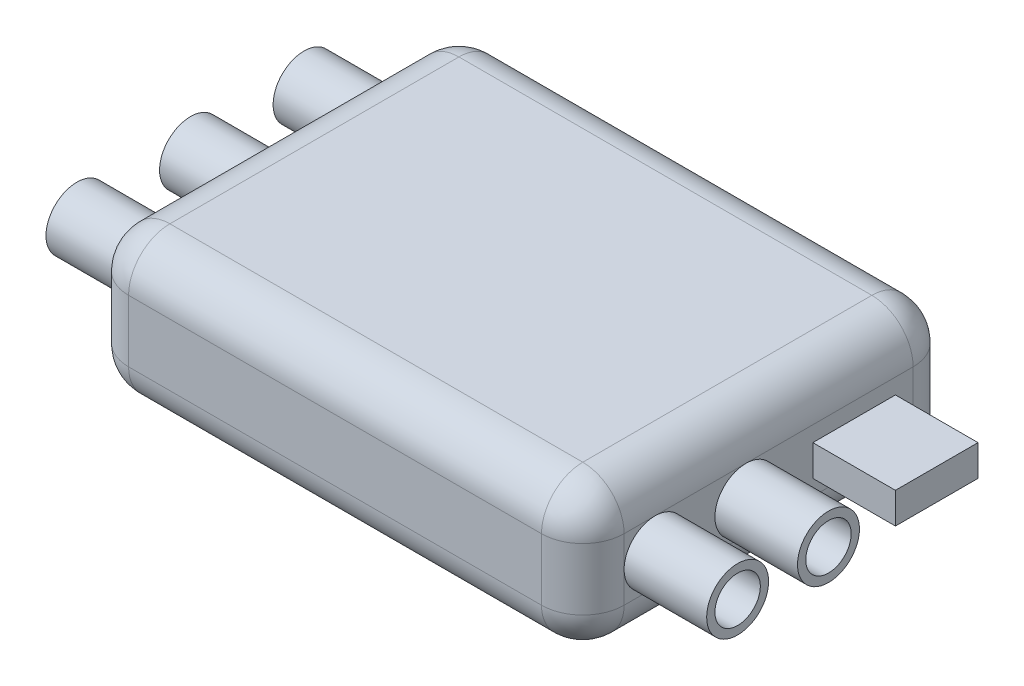
SolidWorks part; units mm, degrees
ref_plane "Front Plane" through (0, 0, 0) normal (0, 0, 1) x (1, 0, 0)
ref_plane "Top Plane" through (0, 0, 0) normal (0, 1, 0) x (1, 0, 0)
ref_plane "Right Plane" through (0, 0, 0) normal (1, 0, 0) x (0, 0, -1)
sketch "Sketch1" plane through (0, 0, 0) normal (0, 1, 0) x (1, 0, 0)
  line L1 (10, -9) -> (-10, -9)
  line L2 (12, -7) -> (12, 7)
  line L3 (10, 9) -> (-10, 9)
  line L4 (-12, -7) -> (-12, 7)
  line L5 (12, -9) -> (-12, 9) construction
  line L6 (12, 9) -> (-12, -9) construction
  arc A0 (12, 7) -> (10, 9) centre (10, 7) ccw
  arc A1 (10, -9) -> (12, -7) centre (10, -7) ccw
  arc A2 (-10, -9) -> (-12, -7) centre (-10, -7) cw
  arc A3 (-10, 9) -> (-12, 7) centre (-10, 7) ccw
  point P0 (0, 0)
  dimension "D3" = 2
  dimension "D1" = 24
  dimension "D2" = 18
extrude "Boss-Extrude1" add sketch "Sketch1" against normal blind 7
sketch "Sketch3" plane through (0, 0, 0) normal (0, 1, 0) x (1, 0, 0)
  line L0 (-12, 7) -> (12, 7)
  line L1 (-12, -7) -> (12, -7)
  line L2 (-10, 9) -> (-10, -9)
  line L3 (10, 9) -> (10, -9)
sketch "Sketch5" plane through (-12, 0, 0) normal (-1, 0, 0) x (0, 0, 1)
  line L0 (-9, 0) -> (9, 0) construction
  line L1 (-7, 0) -> (7, 0)
  line L2 (-9, -7) -> (-9, 0) construction
  line L3 (-9, -5) -> (-9, -2)
  line L4 (-7, -7) -> (7, -7)
  line L5 (9, -5) -> (9, -2)
  line L6 (-9, -2) -> (-9, 0)
  line L7 (-9, 0) -> (-7, 0)
  line L8 (-9, -5) -> (-9, -7)
  line L9 (-9, -7) -> (-7, -7)
  line L10 (7, -7) -> (9, -7)
  line L11 (9, -7) -> (9, -5)
  line L12 (7, 0) -> (9, 0)
  line L13 (9, 0) -> (9, -2)
  arc A0 (7, 0) -> (9, -2) centre (7, -2) cw
  arc A1 (7, -7) -> (9, -5) centre (7, -5) ccw
  arc A2 (-9, -5) -> (-7, -7) centre (-7, -5) ccw
  arc A3 (-7, 0) -> (-9, -2) centre (-7, -2) ccw
  point P10 (9, -7)
  dimension "D1" = 2
sketch "Sketch6" plane through (0, -7, 0) normal (0, -1, 0) x (1, 0, 0)
  line L0 (-12, 7) -> (12, 7) construction
  line L1 (-12, 7) -> (12, 7) construction
  line L2 (-10, -9) -> (-10, 9) construction
  line L3 (-10, -9) -> (-10, 9) construction
  line L4 (10, -9) -> (10, 9) construction
  line L5 (10, -9) -> (10, 9) construction
  line L6 (-12, -7) -> (12, -7) construction
  line L7 (-12, -7) -> (12, -7) construction
extrude "Cut-Extrude3" cut sketch "Sketch5" against normal through all contours A3 L7 L6 | A2 L8 L9 | A1 L10 L11 | L12 A0 L13 region at (-12, -0.4467, -8.5533) region at (-12, -0.4467, 8.5533) region at (-12, -6.5533, -8.5533) region at (-12, -6.5533, 8.5533)
sketch "Sketch7" plane through (-12, 0, 0) normal (-1, 0, 0) x (0, 0, 1)
  line L0 (-9, -2) -> (9, -2)
  line L1 (-9, -5) -> (9, -5)
  line L2 (-9, -3.5) -> (9, -3.5) construction
  line L3 (-9, -5) -> (-9, -2) construction
  line L4 (9, -5) -> (9, -2) construction
  line L5 (-7, -2) -> (-7, -5) construction
  line L6 (-7, -7) -> (-7, 0) construction
  line L7 (-7, -5) -> (7, -5) construction
  line L8 (0, 0) -> (0, -7) construction
  line L9 (-9, -7) -> (9, -7) construction
  line L10 (7, -2) -> (7, -5) construction
  arc A0 (7, -7) -> (9, -5) centre (7, -5) ccw construction
  circle A1 centre (-5.5, -3.5) radius 1.5
  circle A2 centre (0, -3.5) radius 1.5
  circle A3 centre (5.5, -3.5) radius 1.5
  circle A4 centre (-5.5, -3.5) radius 1.1
  circle A5 centre (0, -3.5) radius 1.1
  circle A6 centre (5.5, -3.5) radius 1.1
  point P32 (0, -3.5)
  dimension "D3" = 2.2
  dimension "D1" = 1.5
  dimension "D2" = 1.5
extrude "Boss-Extrude3" add sketch "Sketch7" along normal blind 4 contours A1 A4 | A2 A5 | A3 A6 region at (-12, -2.4693, -4.4693) region at (-12, -2.4693, 1.0307) region at (-12, -2.4693, 6.5307)
sketch "Sketch8" plane through (12, 0, 0) normal (1, 0, 0) x (0, 0, -1)
  line L0 (-9, -2) -> (9, -2) construction
  line L1 (-9, -5) -> (-9, -2) construction
  line L2 (9, -2) -> (9, -5) construction
  line L3 (9, -5) -> (9, -2) construction
  line L4 (9, -5) -> (-9, -5) construction
  line L5 (-9, -5) -> (-9, -2) construction
  line L6 (-9, -3.5) -> (9, -3.5) construction
  line L7 (0, 0) -> (0, -7) construction
  line L8 (9, -7) -> (-9, -7) construction
  line L9 (-5.5, 0) -> (-5.5, -7) construction
  line L10 (9, 0) -> (-9, 0) construction
  line L11 (-7, -7) -> (-7, 0) construction
  line L12 (-7, -2) -> (-7, -5) construction
  line L14 (6.1421, -4.25) -> (2.1421, -4.25)
  line L15 (6.1421, -4.25) -> (6.1421, -2.75)
  line L16 (6.1421, -2.75) -> (2.1421, -2.75)
  line L17 (2.1421, -4.25) -> (2.1421, -2.75)
  line L18 (6.1421, -4.25) -> (2.1421, -2.75) construction
  line L19 (6.1421, -2.75) -> (2.1421, -4.25) construction
  arc A0 (-7, 0) -> (-9, -2) centre (-7, -2) ccw construction
  arc A1 (7, -7) -> (9, -5) centre (7, -5) ccw construction
  circle A2 centre (-5.5, -3.5) radius 1.5
  circle A3 centre (-1.1, -3.5) radius 1.5
  circle A4 centre (-5.5, -3.5) radius 1.1
  circle A5 centre (-1.1, -3.5) radius 1.1
  point P38 (4.1421, -3.5)
  dimension "D2" = 2.2
  dimension "D3" = 4
  dimension "D5" = 4.4
  dimension "D1" = 1.5
  dimension "D4" = 1.5
extrude "Boss-Extrude4" add sketch "Sketch8" along normal blind 4
fillet "Fillet1" radius 2 12 edges at (-11.4142, -0.5858, -8.4142) (-11.4142, -0.5858, 8.4142) (-11.4142, -6.4142, -8.4142) (-11.4142, -6.4142, 8.4142) (11.4142, -6.4142, 8.4142) (11.4142, -6.4142, -8.4142) (11.4142, -0.5858, 8.4142) (11.4142, -0.5858, -8.4142) (-12, 0, 0) (-12, -7, 0) (12, -7, 0) (12, 0, 0)
